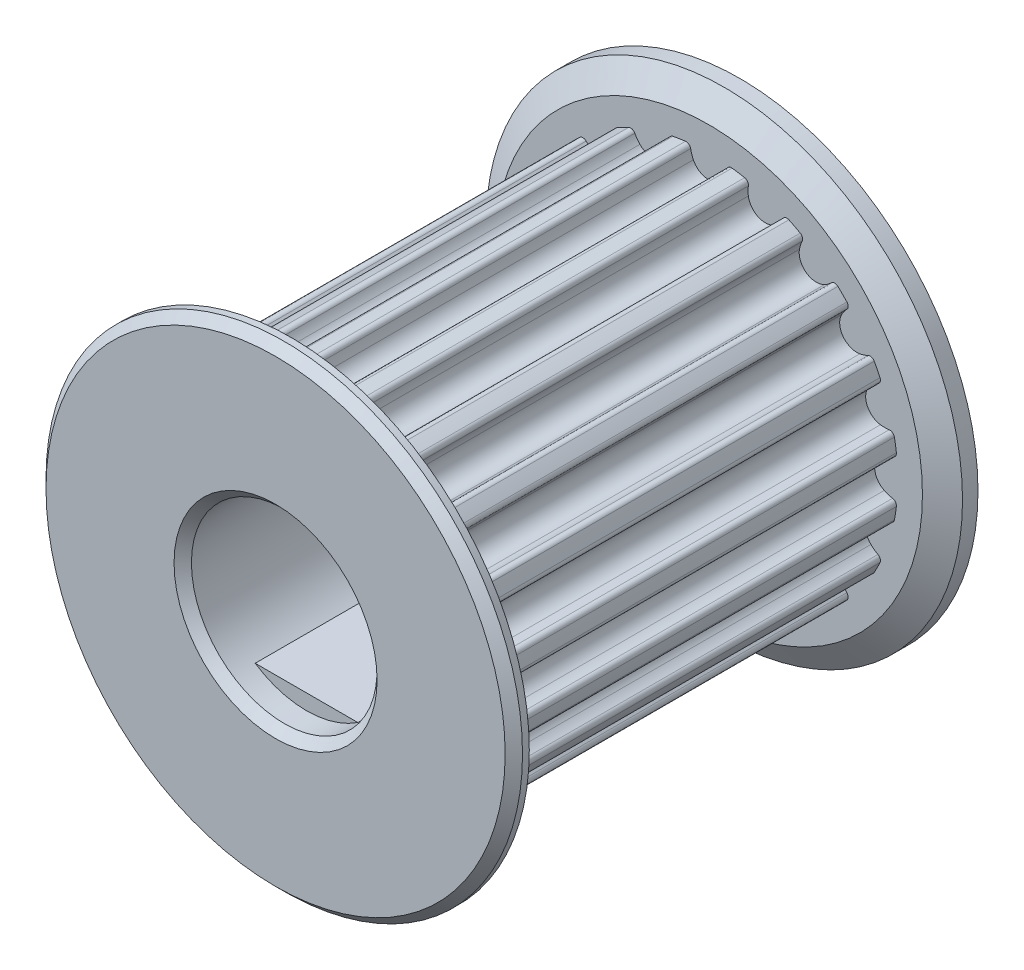
SolidWorks part; units mm, degrees
ref_plane "Front Plane" through (0, 0, 0) normal (0, 0, 1) x (1, 0, 0)
ref_plane "Top Plane" through (0, 0, 0) normal (0, 1, 0) x (1, 0, 0)
ref_plane "Right Plane" through (0, 0, 0) normal (1, 0, 0) x (0, 0, -1)
sketch "Sketch1" plane through (0, 0, 0) normal (0, 0, 1) x (1, 0, 0)
  line L1 (-1.7499, 5.3585) -> (1.7499, 5.3585) construction
  line L4 (0, 0) -> (0, 5.3585) construction
  line L5 (0, 5.3585) -> (0, 11.2107) construction
  line L6 (0, 6.3625) -> (1.9751, 6.0482) construction
  line L7 (1.9751, 6.0482) -> (2.6648, 5.8229) construction
  line L8 (1.9751, 6.0482) -> (1.7499, 5.3585) construction
  line L9 (-1.9751, 6.0482) -> (-1.7499, 5.3585) construction
  line L10 (-1.8963, 5.8067) -> (-2.5144, 7.6995)
  line L11 (-2.5144, 7.6995) -> (2.5144, 7.6995)
  line L12 (2.5144, 7.6995) -> (1.8963, 5.8067)
  circle A0 centre (0, 0) radius 6.3625 construction
  circle A1 centre (0, 0) radius 7.6995 construction
  circle A2 centre (0, 0) radius 6.1085 construction
  arc A3 (-0.4989, 5.6703) -> (0.4989, 5.6703) centre (0, 5.9135) ccw
  arc A4 (-0.4989, 5.6703) -> (-0.5855, 5.9387) centre (0.4, 6.1085) cw
  arc A5 (-1.8963, 5.8067) -> (-0.7518, 6.0621) centre (0, 0) cw
  arc A6 (-0.5855, 5.9387) -> (-0.7518, 6.0621) centre (-0.7333, 5.9132) ccw
  arc A7 (1.8963, 5.8067) -> (0.7518, 6.0621) centre (0, 0) ccw
  arc A8 (0.5855, 5.9387) -> (0.7518, 6.0621) centre (0.7333, 5.9132) cw
  arc A9 (0.4989, 5.6703) -> (0.5855, 5.9387) centre (-0.4, 6.1085) ccw
  point P6 (0, 20.9083)
  point P11 (0, 6.3625)
  point P13 (0, 7.6995)
  point P14 (0, 6.1085)
  dimension "D1" = 9.6976
  dimension "PD" = 12.725
  dimension "D2" = 4.8482
  dimension "OD" = 15.399
  dimension "R3" = 0.555
  dimension "R2" = 1
  dimension "R1" = 0.15
  dimension "b" = 0.4
  dimension "D3" = 2
  dimension "PLD" = 0.254
  dimension "h" = 0.75
sketch "Sketch2" plane through (0, 0, 0) normal (1, 0, 0) x (0, 0, -1)
  line L0 (-7.5, 3) -> (7.5, 3)
  line L1 (-7.5, 3) -> (-7.5, 7.6995)
  line L2 (-7, 7.6995) -> (-7.5, 7.6995)
  line L3 (-7.5, 3) -> (-7.5, 7.6995) construction
  line L4 (-7.5, 7.6995) -> (-6.5, 7.6995) construction
  line L5 (-6.5, 7.6995) -> (-6.5, 6.1085) construction
  line L6 (-6.5, 6.1085) -> (6.5, 6.1085)
  line L7 (6.5, 6.1085) -> (6.5, 7.6995) construction
  line L8 (6.5, 7.6995) -> (7.5, 7.6995) construction
  line L9 (7.5, 7.6995) -> (7.5, 3)
  line L10 (-7.5, 0) -> (7.5, 0) construction
  line L11 (7, 7.6995) -> (6.5, 6.904)
  line L12 (-6.5, 6.904) -> (-7, 7.6995)
  line L14 (-6.5, 6.904) -> (-6.5, 6.1085)
  line L15 (6.5, 6.1085) -> (6.5, 6.904)
  line L16 (7, 7.6995) -> (7.5, 7.6995)
  arc A0 (-6.5, 6.904) -> (-7, 7.6995) centre (-7.3828, 6.904) ccw construction
  arc A1 (6.5, 6.904) -> (7, 7.6995) centre (7.3828, 6.904) cw construction
  point P12 (-6.5, 6.904)
  point P14 (-7, 7.6995)
  point P20 (6.5, 6.904)
  point P21 (7, 7.6995)
  point P25 (6.5, 0)
  point P26 (-6.5, 0)
  dimension "OA" = 15
  dimension "Bore" = 6
  dimension "Outside Width" = 14
  dimension "Inside Width" = 13
revolve "Revolve1" add sketch "Sketch2" angle 360 mid plane about L10
sketch "Sketch3" plane through (0, 0, 0) normal (0, 0, 1) x (1, 0, 0)
  line L6 (2.5144, 7.6995) -> (-2.5144, 7.6995)
  line L7 (1.8963, 5.8067) -> (2.5144, 7.6995)
  line L8 (-2.5144, 7.6995) -> (-1.8963, 5.8067)
  line L9 (2.5144, 7.6995) -> (-2.5144, 7.6995)
  line L10 (1.8963, 5.8067) -> (2.5144, 7.6995)
  line L11 (-2.5144, 7.6995) -> (-1.8963, 5.8067)
  arc A8 (1.8963, 5.8067) -> (0.7518, 6.0621) centre (0, 0) ccw
  arc A9 (0.7518, 6.0621) -> (0.5855, 5.9387) centre (0.7333, 5.9132) ccw
  arc A10 (0.4989, 5.6703) -> (0.5855, 5.9387) centre (-0.4, 6.1085) ccw
  arc A11 (-0.4989, 5.6703) -> (0.4989, 5.6703) centre (0, 5.9135) ccw
  arc A12 (-0.5855, 5.9387) -> (-0.4989, 5.6703) centre (0.4, 6.1085) ccw
  arc A13 (-0.5855, 5.9387) -> (-0.7518, 6.0621) centre (-0.7333, 5.9132) ccw
  arc A14 (-0.7518, 6.0621) -> (-1.8963, 5.8067) centre (0, 0) ccw
  arc A15 (1.8963, 5.8067) -> (0.7518, 6.0621) centre (0, 0) ccw
  arc A16 (0.7518, 6.0621) -> (0.5855, 5.9387) centre (0.7333, 5.9132) ccw
  arc A17 (0.4989, 5.6703) -> (0.5855, 5.9387) centre (-0.4, 6.1085) ccw
  arc A18 (-0.4989, 5.6703) -> (0.4989, 5.6703) centre (0, 5.9135) ccw
  arc A19 (-0.5855, 5.9387) -> (-0.4989, 5.6703) centre (0.4, 6.1085) ccw
  arc A20 (-0.5855, 5.9387) -> (-0.7518, 6.0621) centre (-0.7333, 5.9132) ccw
  arc A21 (-0.7518, 6.0621) -> (-1.8963, 5.8067) centre (0, 0) ccw
  dimension "D1" = 0
extrude "Cut-Extrude1" cut sketch "Sketch3" against normal up to vertex (6.5 mm away) from vertex up to point (0, 6.1085, -6.5) starting at point (0, 6.1085, 6.5)
pattern_circular "CirPattern1" count 20 over 360 about axis through (0, 0, 7.5) along (0, 0, 1) of "Cut-Extrude1"
sketch "Sketch4" plane through (0, 0, 0) normal (1, 0, 0) x (0, -1, 0)
  line L0 (0, -6.5) -> (0, -7.5) construction
  line L1 (-3, -7.5) -> (3, -7.5) construction
  line L2 (6.904, -6.5) -> (-6.904, -6.5) construction
  circle A0 centre (0, -7) radius 1.7526
  dimension "Set Screw" = 3.5052
ref_plane "Plane1" through (0, 0, 7) normal (0, 0, 1) x (1, 0, 0)
chamfer "Chamfer1" distance 0.2807 angle 45 2 edges at (3, 0, 7.5) (7.6995, 0, 7.5)
ref_axis "Center Axis 1" through (0, 0, -7.5) along (0, 0, 1)
ref_plane "Contact Plane 1" through (0, 0, 7.5) normal (0, 0, 1) x (1, 0, 0)
ref_plane "Contact Plane 2" through (0, 0, -7.5) normal (0, 0, -1) x (-1, 0, 0)
sketch "Sketch5" plane through (0, 0, -7.5) normal (0, 0, -1) x (-1, 0, 0)
  line L0 (-1.6583, -2.5) -> (1.6583, -2.5)
  line L1 (-1.6583, -2.5) -> (-1.6583, -3)
  line L2 (-1.6583, -3) -> (1.6583, -3)
  line L3 (1.6583, -3) -> (1.6583, -2.5)
  circle A0 centre (0, 0) radius 3 construction
  dimension "D1" = 2.5
  dimension "D2" = 0.5
extrude "Boss-Extrude1" add sketch "Sketch5" against normal blind 14
